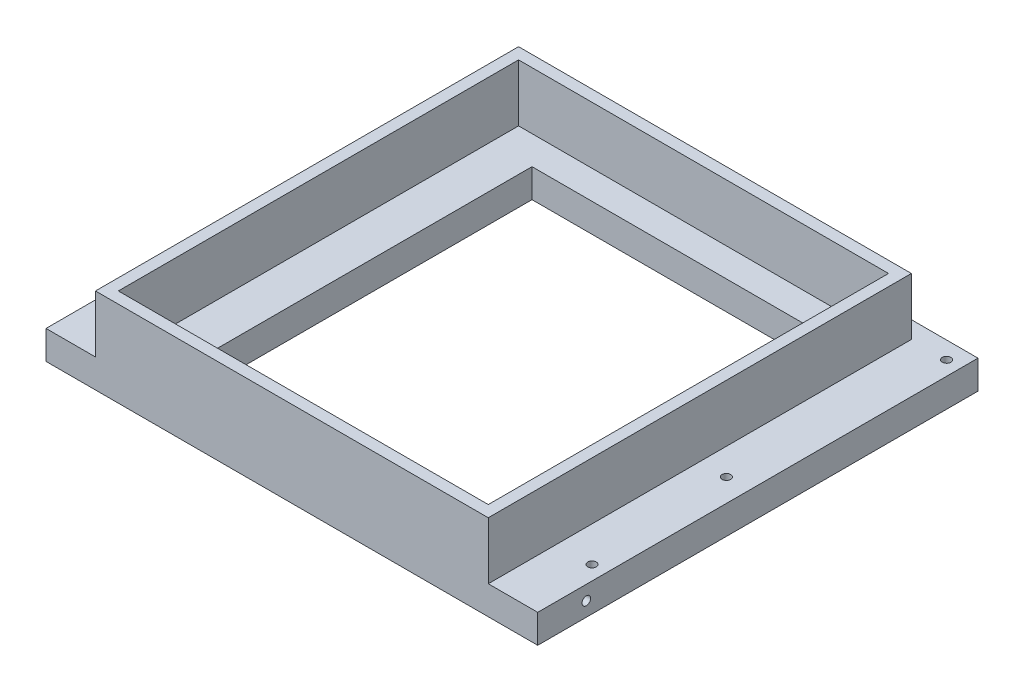
SolidWorks part; units mm, degrees
ref_plane "前视基准面" through (0, 0, 0) normal (0, 0, 1) x (1, 0, 0)
ref_plane "上视基准面" through (0, 0, 0) normal (0, 1, 0) x (1, 0, 0)
ref_plane "右视基准面" through (0, 0, 0) normal (1, 0, 0) x (0, 0, -1)
other "Configuration Table"
sketch "草图1" plane through (0, 0, 0) normal (0, 1, 0) x (1, 0, 0)
  line L1 (-43, -60.5) -> (43, -60.5)
  line L2 (-43, -60.5) -> (-43, 60.5)
  line L3 (-43, 60.5) -> (43, 60.5)
  line L4 (43, -60.5) -> (43, 60.5)
  line L5 (-43, -60.5) -> (43, 60.5) construction
  line L6 (-43, 60.5) -> (43, -60.5) construction
  line L7 (-25, 50.5) -> (25, 50.5)
  line L8 (-25, 50.5) -> (-25, -4.5)
  line L9 (-25, -4.5) -> (25, -4.5)
  line L10 (25, 50.5) -> (25, -4.5)
  line L11 (-25, -25.5) -> (25, -25.5)
  line L12 (-25, -25.5) -> (-25, -50.5)
  line L13 (-25, -50.5) -> (25, -50.5)
  line L14 (25, -25.5) -> (25, -50.5)
  line L15 (-43, -60.5) -> (43, -60.5)
  line L16 (-43, -60.5) -> (-43, -113.5)
  line L17 (-43, -113.5) -> (43, -113.5)
  line L18 (43, -60.5) -> (43, -113.5)
  line L19 (-38, -65.5) -> (38, -65.5)
  line L20 (-38, -65.5) -> (-38, -108.5)
  line L21 (-38, -108.5) -> (38, -108.5)
  line L22 (38, -65.5) -> (38, -108.5)
  point P0 (0, 0)
  dimension "D1" = 86
  dimension "D2" = 121
  dimension "D3" = 10
  dimension "D4" = 18
  dimension "D5" = 18
  dimension "D6" = 55
  dimension "D7" = 10
  dimension "D8" = 25
  dimension "D9" = 5
  dimension "D10" = 5
  dimension "D11" = 5
  dimension "D12" = 5
  dimension "D13" = 53
extrude "凸台-拉伸1" add sketch "草图1" along normal blind 5 contours L18 L1 L16 L17 L19 L22 L21 L20 | L2 L3 L4 L1 | L9 L10 L7 L8 | L11 L14 L13 L12 region at (0, 0, 61.5102)
sketch "草图4" plane through (0, 5, 0) normal (0, 1, 0) x (1, 0, 0)
  line L0 (-43, 60.5) -> (43, 60.5) construction
  line L1 (-34.35, 57.5) -> (34.35, 57.5)
  line L2 (-34.35, 57.5) -> (-34.35, -57.5)
  line L3 (-34.35, -57.5) -> (34.35, -57.5)
  line L4 (34.35, 57.5) -> (34.35, -57.5)
  line L5 (-32.35, -18.5) -> (32.35, -18.5)
  line L6 (-32.35, -18.5) -> (-32.35, -55.5)
  line L7 (-32.35, -55.5) -> (32.35, -55.5)
  line L8 (32.35, -18.5) -> (32.35, -55.5)
  line L9 (32.35, -14.5) -> (-32.35, -14.5)
  line L10 (32.35, -14.5) -> (32.35, 55.5)
  line L11 (32.35, 55.5) -> (-32.35, 55.5)
  line L12 (-32.35, -14.5) -> (-32.35, 55.5)
  line L13 (43, 60.5) -> (43, -113.5) construction
  line L14 (-43, 60.5) -> (-43, -113.5) construction
  dimension "D1" = 5
  dimension "D2" = 10.65
  dimension "D3" = 10.65
  dimension "D4" = 2
  dimension "D5" = 2
  dimension "D6" = 2
  dimension "D7" = 70
  dimension "D8" = 79
  dimension "D9" = 37
  dimension "D10" = 2
extrude "凸台-拉伸2" add sketch "草图4" along normal blind 10 contours L3 L4 L1 L2 | L6 L7 L8 L5 | L12 L11 L10 L9
sketch "草图5" plane through (0, 5, 0) normal (0, 1, 0) x (1, 0, 0)
  line L0 (-43, 60.5) -> (-43, -113.5) construction
  line L1 (43, 60.5) -> (43, -113.5) construction
  line L2 (-43, 60.5) -> (43, 60.5) construction
  line L3 (-43, -85.5) -> (-38, -85.5)
  line L4 (-38, -65.5) -> (-38, -108.5) construction
  line L5 (-23.6333, -57.5) -> (-23.6333, -113.5)
  line L6 (-34.35, -57.5) -> (34.35, -57.5) construction
  line L7 (-43, -113.5) -> (43, -113.5) construction
  line L8 (38, -85.5) -> (43, -85.5)
  line L9 (38, -65.5) -> (38, -108.5) construction
  line L10 (-25, -25.5) -> (-25, -50.5) construction
  line L12 (-34.35, 57.5) -> (34.35, 57.5) construction
  line L13 (-25, -4.5) -> (25, -4.5) construction
  circle A0 centre (-39, 20.5) radius 0.75
  circle A1 centre (39, 20.5) radius 0.75
  circle A2 centre (-39, -32.5) radius 0.75
  circle A3 centre (39, -32.5) radius 0.75
  circle A4 centre (-40.1428, -60.35) radius 0.75
  circle A5 centre (40.1428, -60.35) radius 0.75
  circle A6 centre (-40.1428, -110.5303) radius 0.75
  circle A7 centre (40.1428, -110.5303) radius 0.75
  circle A8 centre (-40.5, 57.5) radius 0.75
  circle A9 centre (-40.5, -38) radius 0.75
  circle A10 centre (-40.5, -85.5) radius 0.75
  circle A11 centre (40.5, 57.5) radius 0.75
  circle A12 centre (40.5, -38) radius 0.75
  circle A13 centre (40.5, -85.5) radius 0.75
  circle A14 centre (-40.5, -4.5) radius 0.75
  circle A15 centre (40.5, -4.5) radius 0.75
  point P40 (-23.6333, -85.5)
  point P52 (-25, -38)
  dimension "D1" = 1.5
  dimension "D2" = 4
  dimension "D3" = 4
  dimension "D4" = 40
  dimension "D5" = 93
extrude "切除-拉伸1" cut sketch "草图5" against normal through all contours A0 | A2 | A4 | A6 | A7 | A5 | A3 | A1 | A8 | A11 | A9 | A12 | A10 | A13 | A14 | A15
sketch "草图7" plane through (0, 5, 0) normal (0, 1, 0) x (1, 0, 0)
  line L0 (42.9928, -57.5) -> (-42.9928, -57.5) construction
  line L1 (-32, -57.5) -> (-17, -57.5)
  line L2 (-32, -57.5) -> (-32, -65.5)
  line L3 (-32, -65.5) -> (-17, -65.5)
  line L4 (-17, -57.5) -> (-17, -65.5)
  line L5 (-43, 60.5) -> (-43, -113.5) construction
  line L6 (-38, -65.5) -> (38, -65.5) construction
  line L8 (-34.35, -57.5) -> (34.35, -57.5) construction
  line L9 (-13, -57.5) -> (13, -57.5)
  line L10 (-13, -57.5) -> (-13, -65.5)
  line L11 (-13, -65.5) -> (13, -65.5)
  line L12 (13, -57.5) -> (13, -65.5)
  line L13 (-38, -65.5) -> (-38, -108.5) construction
  line L14 (-43, -73.5) -> (-38, -73.5)
  line L15 (-43, -73.5) -> (-43, -83.5)
  line L16 (-43, -83.5) -> (-38, -83.5)
  line L17 (-38, -73.5) -> (-38, -83.5)
  line L18 (-43, -113.5) -> (43, -113.5) construction
  line L19 (-43, -95.3803) -> (-38, -95.3803)
  line L20 (-43, -95.3803) -> (-43, -107.5)
  line L21 (-43, -107.5) -> (-38, -107.5)
  line L22 (-38, -95.3803) -> (-38, -107.5)
  line L23 (-42.9928, -113.3803) -> (42.9928, -113.3803) construction
  line L24 (-38, -108.5) -> (38, -108.5) construction
  line L25 (-35, -108.5) -> (-29, -108.5)
  line L26 (-35, -108.5) -> (-35, -113.5)
  line L27 (-35, -113.5) -> (-29, -113.5)
  line L28 (-29, -108.5) -> (-29, -113.5)
  line L29 (43, 60.5) -> (43, -113.5) construction
  line L30 (-6, -108.5) -> (0, -108.5)
  line L31 (-6, -108.5) -> (-6, -113.5)
  line L32 (-6, -113.5) -> (0, -113.5)
  line L33 (0, -108.5) -> (0, -113.5)
  line L34 (14, -108.5) -> (21, -108.5)
  line L35 (14, -108.5) -> (14, -113.5)
  line L36 (14, -113.5) -> (21, -113.5)
  line L37 (21, -108.5) -> (21, -113.5)
  line L38 (27, -108.5) -> (34, -108.5)
  line L39 (27, -108.5) -> (27, -113.5)
  line L40 (27, -113.5) -> (34, -113.5)
  line L41 (34, -108.5) -> (34, -113.5)
  line L42 (43, -81.5) -> (38, -81.5)
  line L43 (43, -81.5) -> (43, -102.5)
  line L44 (43, -102.5) -> (38, -102.5)
  line L45 (38, -81.5) -> (38, -102.5)
  line L46 (38, -65.5) -> (38, -108.5) construction
  dimension "D1" = 11
  dimension "D2" = 26
  dimension "D3" = 30
  dimension "D4" = 56
  dimension "D5" = 16
  dimension "D6" = 26
  dimension "D7" = 6
  dimension "D8" = 18
  dimension "D9" = 8
  dimension "D10" = 14
  dimension "D11" = 37
  dimension "D12" = 43
  dimension "D13" = 57
  dimension "D14" = 64
  dimension "D15" = 70
  dimension "D16" = 77
  dimension "D17" = 11
  dimension "D18" = 32
extrude "切除-拉伸2" cut sketch "草图7" against normal blind 2
sketch "草图8" plane through (-43, 0, 0) normal (-1, 0, 0) x (0, 0, 1)
  line L0 (0, 0) -> (0, 5)
  line L1 (-57.5, 5) -> (57.5, 5) construction
  circle A0 centre (8, 2.5) radius 0.75
  circle A1 centre (23, 2.5) radius 0.75
  circle A2 centre (52, 2.5) radius 0.75
  circle A3 centre (63, 2.5) radius 0.75
  point P13 (0, 2.5)
  dimension "D1" = 1.5
  dimension "D2" = 8
  dimension "D3" = 15
  dimension "D4" = 29
  dimension "D5" = 11
extrude "切除-拉伸3" cut sketch "草图8" against normal blind 2 contours A0 | A1 | A2 | A3
extrude "切除-拉伸4" cut sketch "草图8<3>" along normal blind 2 from surface contours A0 | A1 | A2 | A3 starting at face at (43, 3.25, 59.25)
sketch "草图8<3>" plane through (-43, 0, 0) normal (-1, 0, 0) x (0, 0, 1) same geometry as "草图8"
sketch "草图9" plane through (0, 0, 0) normal (0, 1, 0) x (1, 0, 0)
  line L0 (0, -14.5) -> (0, -18.5)
  line L1 (-47.378, 69.2613) -> (49.394, 69.2613)
  line L2 (-47.378, 69.2613) -> (-47.378, -16.5)
  line L3 (-47.378, -16.5) -> (49.394, -16.5)
  line L4 (49.394, 69.2613) -> (49.394, -16.5)
  line L5 (49.394, -16.5) -> (-47.378, -16.5)
  line L6 (49.394, -16.5) -> (49.394, -57.5)
  line L7 (49.394, -57.5) -> (-47.378, -57.5)
  line L8 (-47.378, -16.5) -> (-47.378, -57.5)
  line L9 (-47.378, -57.5) -> (55.1903, -57.5)
  line L10 (-47.378, -57.5) -> (-47.378, -123.0227)
  line L11 (-47.378, -123.0227) -> (55.1903, -123.0227)
  line L12 (55.1903, -57.5) -> (55.1903, -123.0227)
  line L13 (32.35, -14.5) -> (-32.35, -14.5) construction
  line L14 (-32.35, -18.5) -> (32.35, -18.5) construction
  line L15 (-34.35, -57.5) -> (34.35, -57.5) construction
  point P15 (0, -16.5)
extrude "切除-拉伸5" cut sketch "草图9" along normal through all contours L3 L8 L7 L6 | L12 L9 L7 L10 L11 region at (1.008, 0, 37) region at (3.9062, 0, 90.2614)
